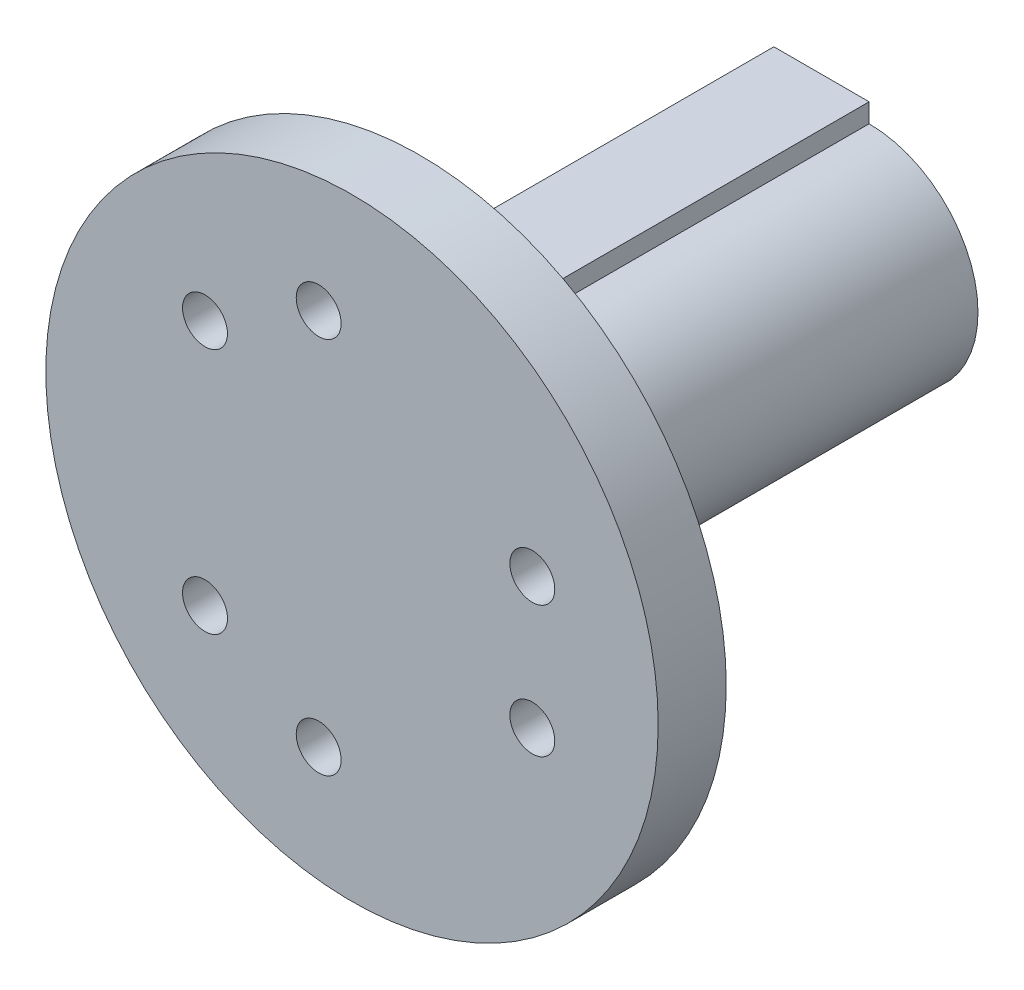
SolidWorks part; units mm, degrees
ref_plane "정면" through (0, 0, 0) normal (0, 0, 1) x (1, 0, 0)
ref_plane "윗면" through (0, 0, 0) normal (0, 1, 0) x (1, 0, 0)
ref_plane "우측면" through (0, 0, 0) normal (1, 0, 0) x (0, 0, -1)
sketch "스케치1" plane through (0, 0, 0) normal (0, 0, 1) x (1, 0, 0)
  line L0 (0, 0) -> (0, 22.5) construction
  line L1 (0, 0) -> (-3.9071, 22.1582) construction
  line L2 (0, 0) -> (-17.236, 14.4627) construction
  circle A0 centre (0, 0) radius 22.5
  circle A1 centre (0, 0) radius 14.1 construction
  circle A2 centre (-2.4484, 13.8858) radius 1.65
  circle A3 centre (-10.8012, 9.0633) radius 1.65
  circle A4 centre (13.2497, 4.8225) radius 1.65
  circle A5 centre (13.2497, -4.8225) radius 1.65
  circle A6 centre (-2.4484, -13.8858) radius 1.65
  circle A7 centre (-10.8012, -9.0633) radius 1.65
  point P22 (0, 0)
  dimension "D1" = 45
  dimension "D2" = 28.2
  dimension "D5" = 3.3
  dimension "D3" = 10
  dimension "D4" = 40
  dimension "D6" = 3
extrude "보스-돌출1" add sketch "스케치1" along normal blind 5
sketch "스케치3" plane through (0, 0, 0) normal (0, 0, -1) x (-1, 0, 0)
  circle A0 centre (2.4484, 13.8858) radius 3
  circle A1 centre (10.8012, 9.0633) radius 3
  circle A2 centre (10.8012, -9.0633) radius 3
  circle A3 centre (2.4484, -13.8858) radius 3
  circle A4 centre (-13.2497, -4.8225) radius 3
  circle A5 centre (-13.2497, 4.8225) radius 3
  dimension "D1" = 6
extrude "컷-돌출1" cut sketch "스케치3" against normal blind 2
sketch "스케치11" plane through (0, 0, 0) normal (0, 0, -1) x (-1, 0, 0)
  circle A0 centre (0, 0) radius 8
extrude "보스-돌출2" add sketch "스케치11" along normal blind 25 contours A0
sketch "스케치12" plane through (0, 0, 0) normal (0, 1, 0) x (1, 0, 0)
  line L0 (-8, 25) -> (-8, 0) construction
  line L1 (0, 25) -> (-8, 25)
  line L2 (0, 25) -> (0, 10)
  line L3 (0, 10) -> (-8, 10)
  line L4 (-8, 25) -> (-8, 10)
  line L5 (8, 25) -> (-8, 25) construction
extrude "컷-돌출9" cut sketch "스케치12" against normal blind 25 and the other way blind 25
sketch "스케치13" plane through (0, 0, 0) normal (-1, 0, 0) x (0, 0, 1)
  line L0 (-25, 0) -> (-25, -9.4) construction
  line L1 (-25, -8) -> (-25, 8) construction
  line L2 (-25, 0) -> (-25, 9.4) construction
  line L3 (-10, 0) -> (-10, -9.4) construction
  line L4 (-10, 8) -> (-10, -8) construction
  line L5 (-10, 0) -> (-10, 9.4) construction
  line L7 (-25, -9.4) -> (-10, -9.4)
  line L8 (-25, -9.4) -> (-25, 9.4)
  line L9 (-25, 9.4) -> (-10, 9.4)
  line L10 (-10, -9.4) -> (-10, 9.4)
  dimension "D1" = 9.4
  dimension "D2" = 9.4
extrude "보스-돌출3" add sketch "스케치13" along normal blind 7
sketch "스케치15" plane through (0, 0, -25) normal (0, 0, -1) x (-1, 0, 0)
  line L0 (0, 8) -> (0, 9.4)
  line L1 (0, -9.4) -> (7, -9.4)
  line L2 (0, -9.4) -> (0, -8)
  line L3 (0, 9.4) -> (7, 9.4)
  line L4 (7, -9.4) -> (7, 9.4)
  arc A0 (0, 8) -> (0, -8) centre (0, 0) ccw
extrude "보스-돌출5" add sketch "스케치15" along normal blind 8
sketch "스케치16" plane through (-7, 0, 0) normal (-1, 0, 0) x (0, 0, 1)
  line L0 (-33, 0) -> (-10, 0) construction
  line L1 (-33, -9.4) -> (-33, 9.4) construction
  line L2 (-10, -3.873) -> (-10, 3.873) construction
  line L3 (-33, 0) -> (-33, -0.6) construction
  line L4 (-33, -0.6) -> (-33, 0.6)
  line L5 (-33, -0.6) -> (-10, -0.6)
  line L6 (-10, -0.6) -> (-10, 0.6)
  line L7 (-33, 0.6) -> (-10, 0.6)
extrude "보스-돌출6" add sketch "스케치16" along normal blind 1
